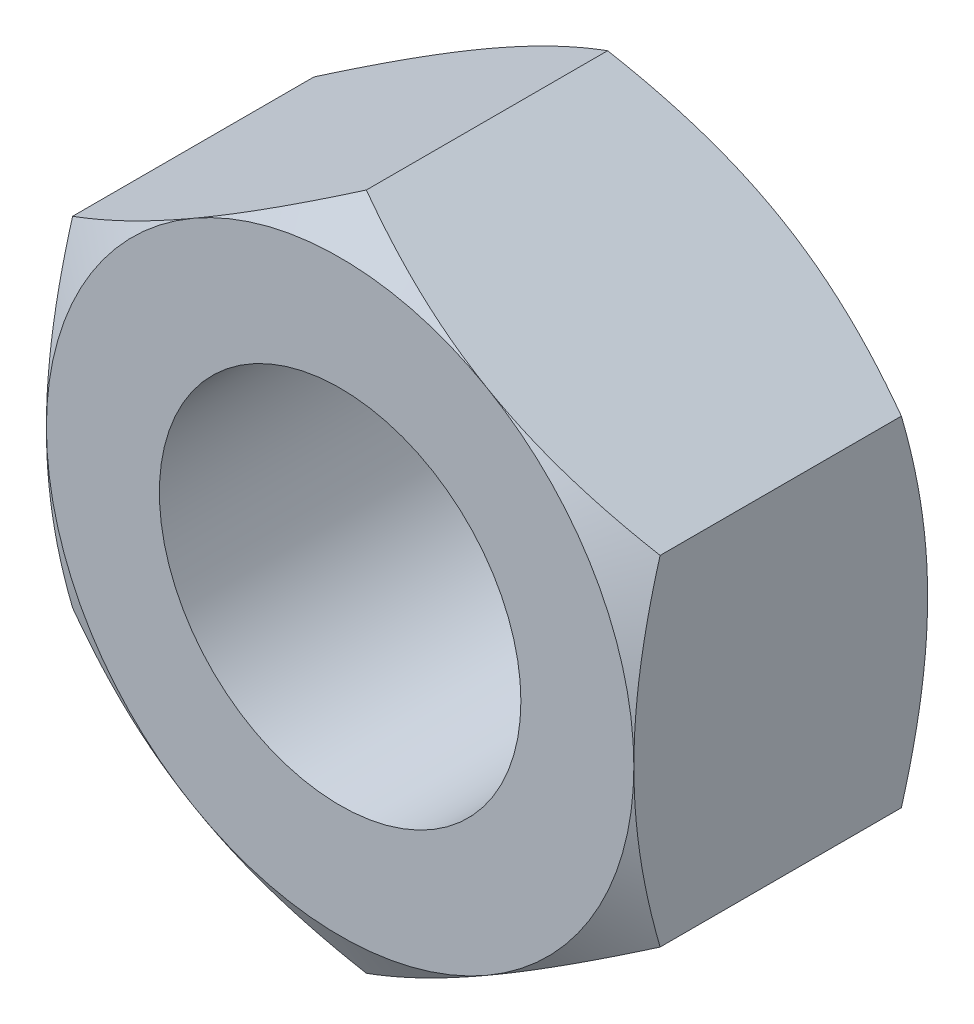
SolidWorks part; units mm, degrees
ref_plane "Plan1" through (0, 0, 0) normal (0, 0, 1) x (1, 0, 0)
ref_plane "Plan2" through (0, 0, 0) normal (0, 1, 0) x (1, 0, 0)
ref_plane "Plan3" through (0, 0, 0) normal (1, 0, 0) x (0, 0, -1)
sketch "Esquisse1" plane through (0, 0, 0) normal (0, 0, 1) x (1, 0, 0)
  line L0 (0, 0) -> (6.5, 0) construction
  line L1 (6.5, -3.7528) -> (6.5, 3.7528)
  line L2 (0, 0) -> (6.5, 3.7528) construction
  line L3 (0, 0) -> (0, 7.5056) construction
  line L4 (6.5, 3.7528) -> (0, 7.5056)
  line L5 (6.5, -3.7528) -> (0, -7.5056)
  line L6 (-6.5, -3.7528) -> (0, -7.5056)
  line L7 (-6.5, -3.7528) -> (-6.5, 3.7528)
  line L8 (-6.5, 3.7528) -> (0, 7.5056)
  circle A0 centre (0, 0) radius 6.5 construction
  circle A1 centre (0, 0) radius 7.5056 construction
  dimension "D2" = 13
  dimension "D1" = 30
extrude "Base-Extrusion" add sketch "Esquisse1" against normal blind 6.5
sketch "Esquisse2" plane through (0, 0, 0) normal (0, 1, 0) x (1, 0, 0)
  line L0 (-6.5, 0) -> (-13.1292, 0)
  line L1 (0, 6.5) -> (0, 0) construction
  line L2 (-6.5, 6.5) -> (-13.1292, 6.5)
  line L3 (-13.1292, 6.5) -> (-13.1292, 0)
  line L5 (-12.1292, 3.25) -> (-6.5, 6.5)
  line L6 (0, 6.5) -> (0, 0) construction
  line L7 (-6.5, 0) -> (-12.1292, 3.25)
  dimension "D1" = 30
  dimension "D2" = 1
  dimension "D3" = 30
revolve "Enlèvement de matière-Révolution1" cut sketch "Esquisse2" angle 360 about L6
sketch "Esquisse3" plane through (0, 0, 0) normal (0, 0, 1) x (1, 0, 0)
  circle A0 centre (0, 0) radius 4
  dimension "D1" = 8
extrude "Enlèv. mat.-Extru.1" cut sketch "Esquisse3" against normal through all
ref_axis "Axe1" through (0, 0, -50) along (0, 0, 1)
